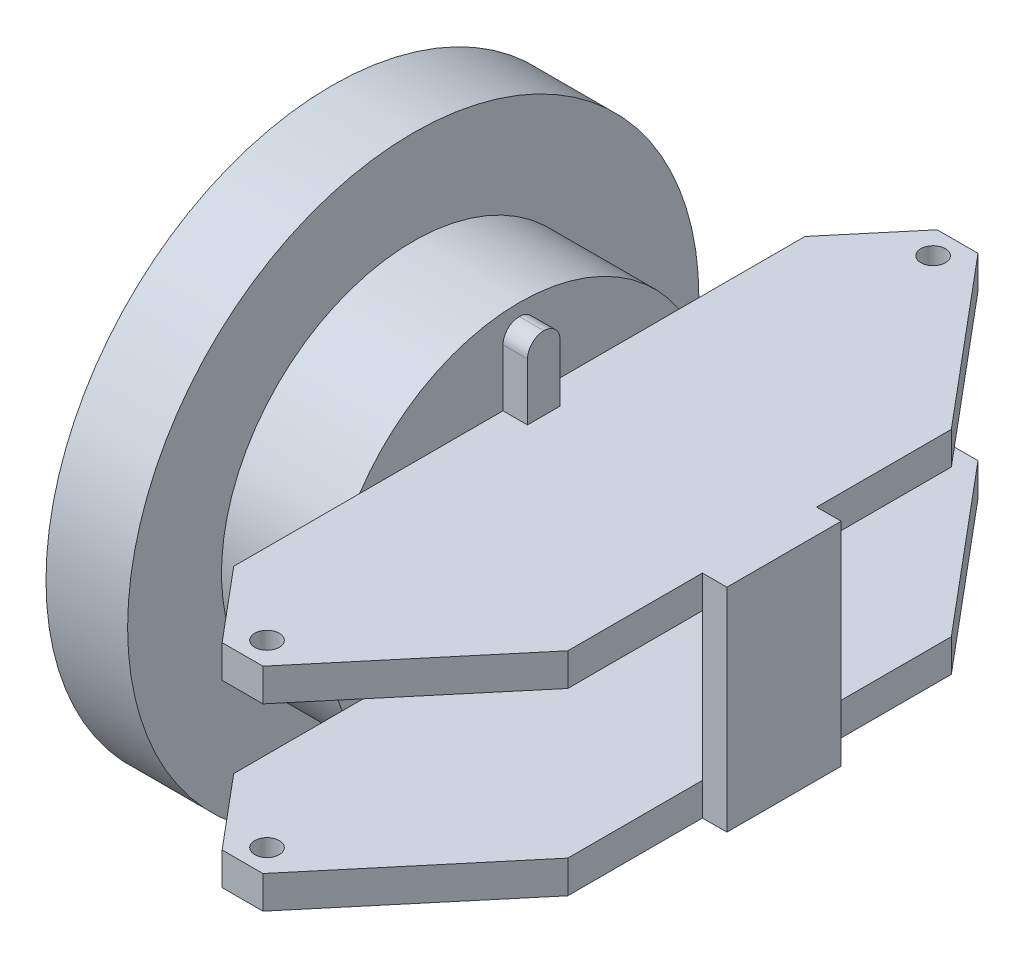
SolidWorks part; units mm, degrees
ref_plane "Front Plane" through (0, 0, 0) normal (0, 0, 1) x (1, 0, 0)
ref_plane "Top Plane" through (0, 0, 0) normal (0, 1, 0) x (1, 0, 0)
ref_plane "Right Plane" through (0, 0, 0) normal (1, 0, 0) x (0, 0, -1)
sketch "Sketch1" plane through (0, 0, 0) normal (1, 0, 0) x (0, 0, -1)
  circle A0 centre (0, 0) radius 35
  dimension "D1" = 70
extrude "Boss-Extrude1" add sketch "Sketch1" along normal blind 10
sketch "Sketch2" plane through (10, 0, 0) normal (1, 0, 0) x (0, 0, -1)
  circle A0 centre (0, 0) radius 23.5
  dimension "D1" = 47
extrude "Boss-Extrude2" add sketch "Sketch2" along normal blind 13
ref_plane "Plane1" through (0, 13, 0) normal (0, -1, 0) x (-1, 0, 0)
sketch "Sketch3" plane through (0, 13, 0) normal (0, -1, 0) x (-1, 0, 0)
  line L0 (-23, 35) -> (-23, -35)
  line L1 (-23, 23.5) -> (-23, -23.5) construction
  line L2 (-23, -35) -> (-30.3921, -43.8095)
  line L3 (-30.3921, -43.8095) -> (-35.3921, -43.8095)
  line L4 (-35.3921, -43.8095) -> (-52.4338, -23.5)
  line L5 (-52.4338, -23.5) -> (-52.4338, 23.5)
  line L6 (-23, 0) -> (-56.1898, 0) construction
  line L7 (-23, 35) -> (-30.3921, 43.8095)
  line L8 (-30.3921, 43.8095) -> (-35.3921, 43.8095)
  line L9 (-35.3921, 43.8095) -> (-52.4338, 23.5)
  line L10 (-23, -23.5) -> (-52.4338, -23.5) construction
  line L11 (-23, -23.5) -> (-10, -23.5) construction
  point P14 (-52.4338, 0)
  dimension "D1" = 35
  dimension "D2" = 11.5
  dimension "D3" = 40
  dimension "D4" = 5
  dimension "D5" = 50
extrude "Boss-Extrude3" add sketch "Sketch3" along normal blind 4
sketch "Sketch4" plane through (0, 13, 0) normal (0, 1, 0) x (1, 0, 0)
  line L0 (35.3921, -43.8095) -> (30.3921, -43.8095) construction
  circle A0 centre (32.8921, -40.8095) radius 1.5
  point P4 (32.8921, -43.8095)
  dimension "D1" = 3
  dimension "D2" = 3
extrude "Cut-Extrude1" cut sketch "Sketch4" against normal blind 4
mirror "Mirror1" about plane through (0, 0, 0) normal (0, 0, 1) of "Cut-Extrude1"
mirror "Mirror2" about plane through (0, 0, 0) normal (0, 1, 0) of "Mirror1", "Cut-Extrude1", "Boss-Extrude3"
sketch "Sketch5" plane through (23, 0, 0) normal (1, 0, 0) x (0, 0, -1)
  line L0 (0, 13) -> (0, 23.5) construction
  line L1 (-28.8386, 13) -> (28.8386, 13) construction
  line L2 (-2, 13) -> (-2, 22)
  line L3 (-2, 22) -> (2, 22)
  line L4 (2, 22) -> (2, 13)
  line L5 (2, 13) -> (-2, 13)
  arc A0 (19.5768, 13) -> (-19.5768, 13) centre (0, 0) ccw construction
  dimension "D1" = 9
  dimension "D2" = 2
  dimension "D3" = 2
extrude "Boss-Extrude4" add sketch "Sketch5" along normal blind 3
fillet "Fillet1" radius 2 2 edges at (24.5, 22, -2) (24.5, 22, 2)
mirror "Mirror3" about plane through (0, 0, 0) normal (0, 1, 0) of "Fillet1", "Boss-Extrude4"
sketch "Sketch6" plane through (52.4338, 0, 0) normal (1, 0, 0) x (0, 0, -1)
  line L1 (-7, -13) -> (7, -13)
  line L2 (-7, -13) -> (-7, 13)
  line L3 (-7, 13) -> (7, 13)
  line L4 (7, -13) -> (7, 13)
  line L5 (-7, -13) -> (7, 13) construction
  line L6 (-7, 13) -> (7, -13) construction
  point P0 (0, 0)
  dimension "D1" = 14
  dimension "D2" = 26
extrude "Boss-Extrude5" add sketch "Sketch6" along normal blind 3
sketch "Sketch7" plane through (0, 0, 0) normal (-1, 0, 0) x (0, 0, 1)
  circle A0 centre (0, 0) radius 10
  dimension "D1" = 20
extrude "Cut-Extrude2" cut sketch "Sketch7" against normal blind 10
